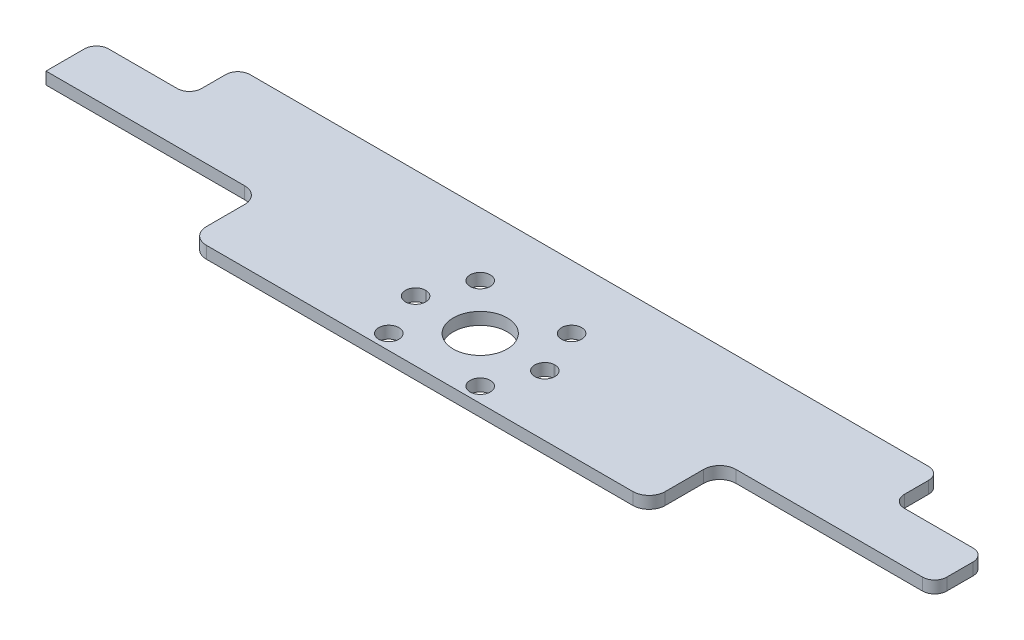
SolidWorks part; units mm, degrees
ref_plane "前视基准面" through (0, 0, 0) normal (0, 0, 1) x (1, 0, 0)
ref_plane "上视基准面" through (0, 0, 0) normal (0, 1, 0) x (1, 0, 0)
ref_plane "右视基准面" through (0, 0, 0) normal (1, 0, 0) x (0, 0, -1)
other "Configuration Table"
sketch "草图2" plane through (0, 0, 0) normal (0, 1, 0) x (1, 0, 0)
  line L0 (110, -9.2483) -> (-110, -9.2483)
  line L1 (110, -26.7483) -> (-110, -26.7483)
  line L2 (110, -26.7483) -> (110, 15.2517)
  line L3 (110, 15.2517) -> (-110, 15.2517)
  line L4 (-110, -26.7483) -> (-110, 15.2517)
  line L6 (-110, 3.2517) -> (-87, 3.2517)
  line L7 (56.8055, -9.2483) -> (56.8055, -26.7483)
  line L8 (0, -9.2483) -> (0, 15.2517)
  line L9 (-56.8055, -9.2483) -> (-56.8055, -26.7483)
  line L10 (-87, 3.2517) -> (-87, 15.2517)
  line L11 (87, 3.2517) -> (87, 15.2517)
  line L12 (110, 3.2517) -> (87, 3.2517)
  circle A0 centre (0, -11.7483) radius 6.682
  circle A1 centre (11.3137, -0.4346) radius 2.5
  circle A2 centre (0, -11.7483) radius 16
  circle A3 centre (16, -11.7483) radius 2.5
  circle A4 centre (11.3137, -23.062) radius 2.5
  circle A5 centre (0, -27.7483) radius 2.5
  circle A6 centre (-11.3137, -23.062) radius 2.5
  circle A7 centre (-16, -11.7483) radius 2.5
  circle A8 centre (-11.3137, -0.4346) radius 2.5
  circle A9 centre (0, 4.2517) radius 2.5
  point P0 (0, 0)
  point P37 (0, -11.7483)
  dimension "D3" = 5
  dimension "D1" = 220
  dimension "D2" = 17.5
  dimension "D5" = 42
  dimension "D7" = 23
  dimension "D8" = 12
  dimension "D4" = 8
extrude "凸台-拉伸1" add sketch "草图2" along normal blind 3 contours A7 A2 A6 L1 A5 A4 A3 L0 A0 | A9 L8 A0 L0 A2 A1 | A9 A2 A8 L0 A0 L8 | A9 L8 L3 L4 L0 A2 A8 | A9 A2 A1 L0 L2 L3 L8 | L1 A5 | A4 A2 L1 L7 L0 A3 | A7 L0 L9 L1 A2 A6 | A9 region at (53.4494, 0, -2.7134) region at (35.6553, 0, 18.309) region at (15.4472, 0, 9.3085) region at (6.9935, 0, 3.4384) region at (0, 0, 26.1296) region at (-53.4494, 0, -2.7134) region at (-6.9935, 0, 3.4384) region at (-35.6553, 0, 18.309)
fillet "圆角1" radius 4 4 edges at (56.8055, 1.5, 9.2483) (56.8055, 1.5, 26.7483) (-56.8055, 1.5, 9.2483) (-56.8055, 1.5, 26.7483)
fillet "圆角2" radius 3 7 edges at (-110, 1.5, -3.2517) (-87, 1.5, -3.2517) (-87, 1.5, -15.2517) (110, 1.5, 9.2483) (110, 1.5, -3.2517) (87, 1.5, -3.2517) (87, 1.5, -15.2517)
